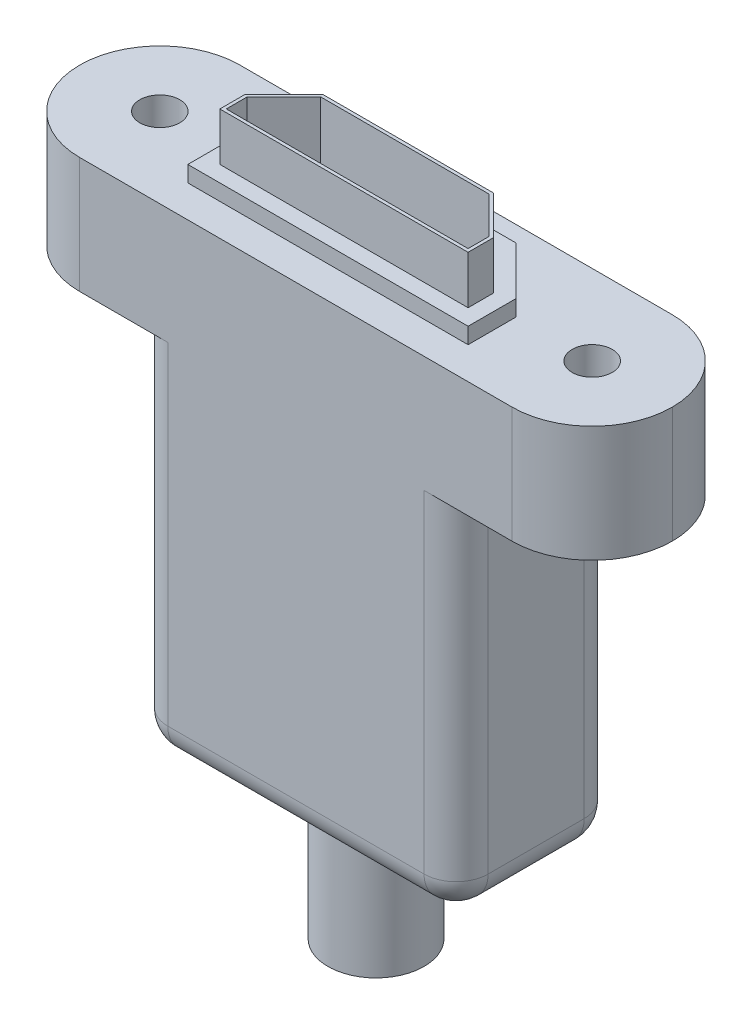
SolidWorks part; units mm, degrees
ref_plane "前视基准面" through (0, 0, 0) normal (0, 0, 1) x (1, 0, 0)
ref_plane "上视基准面" through (0, 0, 0) normal (0, 1, 0) x (1, 0, 0)
ref_plane "右视基准面" through (0, 0, 0) normal (1, 0, 0) x (0, 0, -1)
sketch "草图1" plane through (0, 0, 0) normal (0, 1, 0) x (1, 0, 0)
  line L1 (18.5, -5) -> (-18.5, -5)
  line L2 (18.5, -5) -> (18.5, 5)
  line L3 (18.5, 5) -> (-18.5, 5)
  line L4 (-18.5, -5) -> (-18.5, 5)
  line L5 (18.5, -5) -> (-18.5, 5) construction
  line L6 (18.5, 5) -> (-18.5, -5) construction
  point P0 (0, 0)
  dimension "D1" = 10
  dimension "D2" = 37
extrude "凸台-拉伸1" add sketch "草图1" along normal blind 7.25
sketch "草图2" plane through (0, 7.25, 0) normal (0, 1, 0) x (1, 0, 0)
  line L0 (-8.75, 0) -> (-5.75, 3)
  line L1 (8.75, -3) -> (-8.75, -3)
  line L2 (8.75, -3) -> (8.75, 0)
  line L3 (5.75, 3) -> (-5.75, 3)
  line L4 (-8.75, -3) -> (-8.75, 0)
  line L5 (8.75, -3) -> (-8.75, 3) construction
  line L6 (8.75, 3) -> (-8.75, -3) construction
  line L7 (8.75, 0) -> (5.75, 3)
  point P0 (0, 0)
  dimension "D1" = 17.5
  dimension "D2" = 6
extrude "凸台-拉伸2" add sketch "草图2" along normal blind 4
fillet "圆角1" radius 5 4 edges at (18.5, 3.625, 5) (18.5, 3.625, -5) (-18.5, 3.625, 5) (-18.5, 3.625, -5)
sketch "草图3" plane through (0, 11.25, 0) normal (0, 1, 0) x (1, 0, 0)
  line L0 (7.75, -2) -> (7.75, -0.4142)
  line L1 (7.75, -0.4142) -> (5.3358, 2)
  line L2 (5.3358, 2) -> (-5.3358, 2)
  line L3 (-5.3358, 2) -> (-7.75, -0.4142)
  line L4 (-7.75, -0.4142) -> (-7.75, -2)
  line L5 (-7.75, -2) -> (7.75, -2)
  line L6 (8.75, -3) -> (8.75, 0)
  line L7 (8.75, 0) -> (5.75, 3)
  line L8 (5.75, 3) -> (-5.75, 3)
  line L9 (-5.75, 3) -> (-8.75, 0)
  line L10 (-8.75, 0) -> (-8.75, -3)
  line L11 (-8.75, -3) -> (8.75, -3)
  line L12 (8.75, -3) -> (8.75, 0)
  line L13 (8.75, 0) -> (5.75, 3)
  line L14 (5.75, 3) -> (-5.75, 3)
  line L15 (-5.75, 3) -> (-8.75, 0)
  line L16 (-8.75, 0) -> (-8.75, -3)
  line L17 (-8.75, -3) -> (8.75, -3)
  dimension "D1" = 0
  dimension "D2" = 1
extrude "切除-拉伸1" cut sketch "草图3" against normal blind 3
sketch "草图4" plane through (0, 11.25, 0) normal (0, 1, 0) x (1, 0, 0)
  line L0 (-7.55, -0.4971) -> (-7.55, -1.8)
  line L1 (-7.55, -1.8) -> (7.55, -1.8)
  line L2 (7.55, -1.8) -> (7.55, -0.4971)
  line L3 (7.55, -0.4971) -> (5.2529, 1.8)
  line L4 (5.2529, 1.8) -> (-5.2529, 1.8)
  line L5 (-5.2529, 1.8) -> (-7.55, -0.4971)
  line L6 (-7.75, -0.4142) -> (-7.75, -2)
  line L7 (-7.75, -2) -> (7.75, -2)
  line L8 (7.75, -2) -> (7.75, -0.4142)
  line L9 (7.75, -0.4142) -> (5.3358, 2)
  line L10 (5.3358, 2) -> (-5.3358, 2)
  line L11 (-5.3358, 2) -> (-7.75, -0.4142)
  line L12 (-7.75, -0.4142) -> (-7.75, -2) construction
  line L13 (-7.75, -2) -> (7.75, -2) construction
  line L14 (7.75, -2) -> (7.75, -0.4142) construction
  line L15 (7.75, -0.4142) -> (5.3358, 2) construction
  line L16 (5.3358, 2) -> (-5.3358, 2) construction
  line L17 (-5.3358, 2) -> (-7.75, -0.4142) construction
  dimension "D1" = 0
  dimension "D2" = 0.2
extrude "切除-拉伸3" cut sketch "草图4" against normal blind 4
hole_wizard "M3 螺纹孔1" positions "草图5" profile "草图6" tap size "M3" standard "GB" end condition up to next
sketch "草图5" plane through (0, 7.25, 0) normal (0, 1, 0) x (1, 0, 0)
  line L0 (0, 0) -> (0, 5) construction
  line L1 (13.5, 5) -> (-13.5, 5) construction
  point P0 (-13.5, 0)
  point P2 (13.5, 0)
  dimension "D1" = 27
sketch "草图6" plane through (-13.5, 7.25, 0) normal (1, 0, 0) x (0, 0, 1)
  line L0 (0, 0) -> (0, 7.25)
  line L1 (0, 7.25) -> (1.25, 7.25)
  line L2 (1.25, 7.25) -> (1.25, 0)
  line L5 (1.25, 0) -> (0, 0)
  line L11 (0, -6.35) -> (0, 107.95) construction
  dimension "通孔螺纹孔钻头直径" = 2.5
  dimension "通孔螺纹孔钻头深度" = 7.25
cosmetic thread "孔螺蚊线1" parameters "D2"=3
cosmetic thread "孔螺蚊线2" parameters "D2"=3
sketch "草图7" plane through (0, 0, 0) normal (0, -1, 0) x (1, 0, 0)
  line L0 (-13.5, 5) -> (13.5, 5) construction
  line L1 (10.0017, -5) -> (-10.0017, -5)
  line L2 (10.0017, -5) -> (10.0017, 5)
  line L3 (10.0017, 5) -> (-10.0017, 5)
  line L4 (-10.0017, -5) -> (-10.0017, 5)
  line L5 (10.0017, -5) -> (-10.0017, 5) construction
  line L6 (10.0017, 5) -> (-10.0017, -5) construction
  point P0 (0, 0)
  dimension "D1" = 20.0034
extrude "凸台-拉伸3" add sketch "草图7" along normal blind 22.75
sketch "草图8" plane through (0, -22.75, 0) normal (0, -1, 0) x (1, 0, 0)
  circle A0 centre (0, 0) radius 3
  dimension "D1" = 6
extrude "凸台-拉伸4" add sketch "草图8" along normal blind 8
fillet "圆角2" radius 2 8 edges at (0, -22.75, -5) (-10.0017, -22.75, 0) (0, -22.75, 5) (10.0017, -22.75, 0) (10.0017, -11.375, -5) (10.0017, -11.375, 5) (-10.0017, -11.375, -5) (-10.0017, -11.375, 5)
